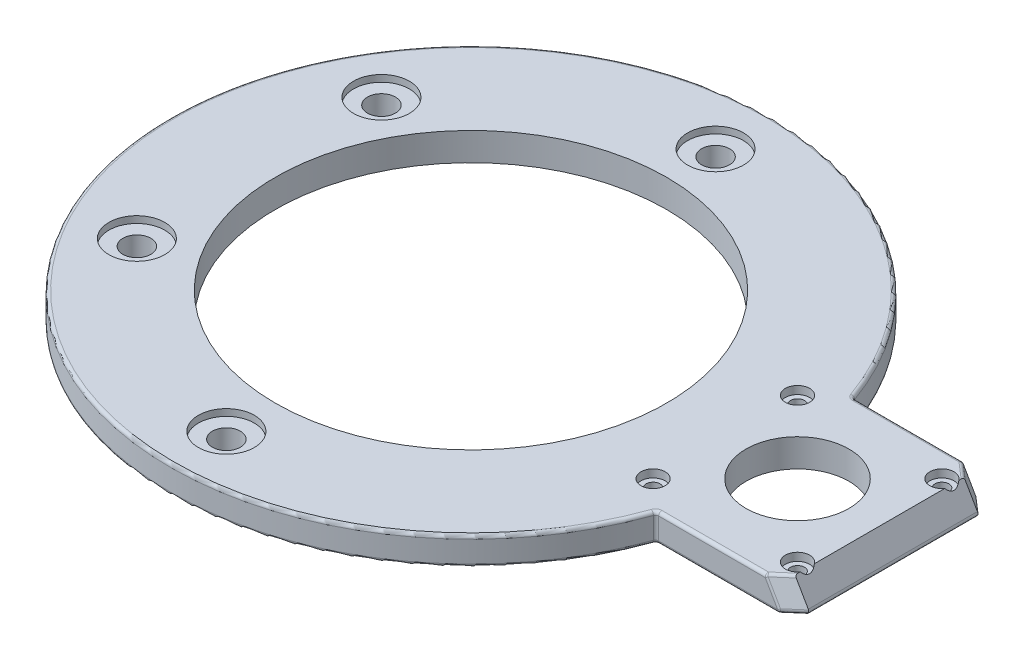
SolidWorks part; units mm, degrees
ref_plane "前视基准面" through (0, 0, 0) normal (0, 0, 1) x (1, 0, 0)
ref_plane "上视基准面" through (0, 0, 0) normal (0, 1, 0) x (1, 0, 0)
ref_plane "右视基准面" through (0, 0, 0) normal (1, 0, 0) x (0, 0, -1)
other "Configuration Table"
sketch "草图1" plane through (0, 0, 0) normal (0, 1, 0) x (1, 0, 0)
  circle A0 centre (0, 0) radius 43
  dimension "D1" = 86
extrude "凸台-拉伸1" add sketch "草图1" along normal blind 4
sketch "草图4" plane through (0, 0, 0) normal (0, 0, 1) x (1, 0, 0)
  line L0 (30, 4) -> (30, 0)
  line L1 (43, 4) -> (-43, 4) construction
  line L2 (-43, 0) -> (43, 0) construction
  line L3 (30, 0) -> (66, 0)
  line L4 (66, 0) -> (64, 4)
  line L5 (64, 4) -> (30, 4)
  dimension "D1" = 34
  dimension "D2" = 30
  dimension "D3" = 36
extrude "凸台-拉伸2" add sketch "草图4" along normal mid plane 40
sketch "草图5" plane through (0, 4, 0) normal (0, 1, 0) x (1, 0, 0)
  circle A0 centre (0, 0) radius 28
  dimension "D1" = 56
extrude "切除-拉伸2" cut sketch "草图5" against normal blind 40
sketch "草图10" plane through (0, 4, 0) normal (0, 1, 0) x (1, 0, 0)
  circle A0 centre (44, 0) radius 15
  dimension "D1" = 30
  dimension "D2" = 44
extrude "切除-拉伸4" cut sketch "草图10" against normal blind 10
scale "缩放比例1" scale about centroid uniform scaling yes scale factor 1.5
sketch "草图14" plane through (0, 5.0037, 0) normal (0, 1, 0) x (1, 0, 0)
  circle A0 centre (63.3359, 0) radius 22.5 construction
  circle A1 centre (63.3359, 0) radius 22.5
extrude "凸台-拉伸3" add sketch "草图14" against normal up to surface (6 mm away) up to face at (63.3359, 5.0037, 22.5)
sketch "草图17" plane through (0, 5.0037, 0) normal (0, 1, 0) x (1, 0, 0)
  circle A0 centre (-2.6641, 0) radius 52.5 construction
  circle A1 centre (-2.6641, 52.5) radius 6
  dimension "D1" = 105
  dimension "D2" = 12
extrude "切除-拉伸10" cut sketch "草图17" against normal blind 1.45 and the other way through all
sketch "草图18" plane through (0, 3.5537, 0) normal (0, 1, 0) x (1, 0, 0)
  circle A0 centre (-2.6641, 52.5) radius 3
  dimension "D1" = 6
extrude "切除-拉伸11" cut sketch "草图18" against normal through all
pattern_circular "阵列(圆周)5" count 4 every 60 about axis through (-2.6641, 5.0037, 0) along (0, 1, 0) of "切除-拉伸10", "切除-拉伸11"
sketch "草图20" plane through (0, 5.0037, 0) normal (0, 1, 0) x (1, 0, 0)
  line L0 (58.2697, 21.15) -> (96.3359, 21.15)
  line L1 (96.3359, -30) -> (96.3359, 30) construction
  line L2 (96.3359, 21.15) -> (96.3359, 0)
  line L3 (96.3359, 0) -> (61.8359, 0)
  line L4 (47.0041, 41.15) -> (96.3359, 41.15)
  line L5 (96.3359, 41.15) -> (96.3359, 21.15)
  arc A0 (54.4345, 30) -> (54.4345, -30) centre (-2.6641, 0) ccw construction
  circle A1 centre (-2.6641, 0) radius 64.5
  arc M8 (54.4345, 30) -> (54.4345, -30) centre (-2.6641, 0) ccw
  line M10 (93.3359, -30) -> (93.3359, 30)
  line M11 (93.3359, 30) -> (54.4345, 30)
  dimension "D1" = 21.15
  dimension "D2" = 20
extrude "切除-拉伸15" cut sketch "草图20" against normal through all contours L5 L4 L0 M8 M11 M10 | A1 L0 M10 M11 region at (74.893, 5.0037, -25.6516) region at (74.6757, 5.0037, -35.2202)
mirror "镜向3" about plane through (0, 0, 0) normal (0, 0, 1) of "切除-拉伸15"
sketch "草图21" plane through (0, 0, 21.15) normal (0, 0, 1) x (1, 0, 0)
  line L0 (85.0359, 5.0037) -> (88.5, -0.9963)
  line L1 (58.2697, 5.0037) -> (93.3359, 5.0037) construction
  line L2 (58.2697, -0.9963) -> (96.3359, -0.9963) construction
  line L3 (88.5, -0.9963) -> (96.3359, -0.9963)
  line L4 (96.3359, -0.9963) -> (93.3359, 5.0037)
  line L5 (93.3359, 5.0037) -> (85.0359, 5.0037)
  dimension "D1" = 88.5
  dimension "D2" = 60
extrude "切除-拉伸16" cut sketch "草图21" against normal through all
chamfer "倒角1" distance 3 angle 45 2 edges at (86.7679, 2.0037, -21.15) (86.7679, 2.0037, 21.15)
sketch "草图22" plane through (0, 5.0037, 0) normal (0, 1, 0) x (1, 0, 0)
  line L0 (88.5, 18.15) -> (88.5, -18.15) construction
  line L1 (51.925, -15.5) -> (82.925, -15.5)
  line L2 (51.925, -15.5) -> (51.925, 15.5)
  line L3 (51.925, 15.5) -> (82.925, 15.5)
  line L4 (82.925, -15.5) -> (82.925, 15.5)
  line L5 (51.925, -15.5) -> (82.925, 15.5) construction
  line L6 (51.925, 15.5) -> (82.925, -15.5) construction
  circle A1 centre (51.925, 15.5) radius 1.5
  circle A2 centre (82.925, 15.5) radius 1.5
  circle A3 centre (82.925, -15.5) radius 1.5
  circle A4 centre (51.925, -15.5) radius 1.5
  point P0 (67.425, 0)
  dimension "D3" = 3
  dimension "D4" = 3
  dimension "D5" = 3
  dimension "D6" = 3
  dimension "D1" = 31
  dimension "D2" = 5.575
extrude "切除-拉伸18" cut sketch "草图22" against normal through all contours A1 | A2 | A3 | A4
sketch "草图23" plane through (0, 5.0037, 0) normal (0, 1, 0) x (1, 0, 0)
  circle A0 centre (82.925, -15.5) radius 2.6
  circle A1 centre (82.925, 15.5) radius 2.6
  circle A2 centre (51.925, 15.5) radius 2.6
  circle A3 centre (51.925, -15.5) radius 2.6
  dimension "D1" = 5.2
  dimension "D2" = 5.2
  dimension "D3" = 5.2
  dimension "D4" = 5.2
extrude "切除-拉伸19" cut sketch "草图23" against normal blind 1.7
sketch "草图24" plane through (0, 5.0037, 0) normal (0, 1, 0) x (1, 0, 0)
  line L0 (51.925, 15.5) -> (82.925, -15.5) construction
  line L1 (82.925, 15.5) -> (51.925, -15.5) construction
  circle A0 centre (67.425, 0) radius 11.05
  dimension "D1" = 22.1
extrude "切除-拉伸20" cut sketch "草图24" against normal through all
fillet "圆角1" radius 0.7 8 edges at (71.6528, -0.9963, -21.15) (69.9208, 5.0037, -21.15) (69.9208, 5.0037, 21.15) (71.6528, -0.9963, 21.15) (58.2697, 2.0037, -21.15) (-67.1641, 5.0037, 0) (58.2697, 2.0037, 21.15) (-67.1641, -0.9963, 0)
fillet "0" radius 0.7 11 edges at (83.708, 5.0037, 19.3) (81.9269, 4.7987, 20.945) (83.3038, 2.0037, 21.15) (85.1543, -0.7913, 20.945) (83.708, 5.0037, -19.3) (81.9269, 4.7987, -20.945) (83.3038, 2.0037, -21.15) (85.1543, -0.7913, -20.945) (87.1721, -0.9963, 19.3) (87.1721, -0.9963, -19.3) (88.5, -0.9963, 0)
